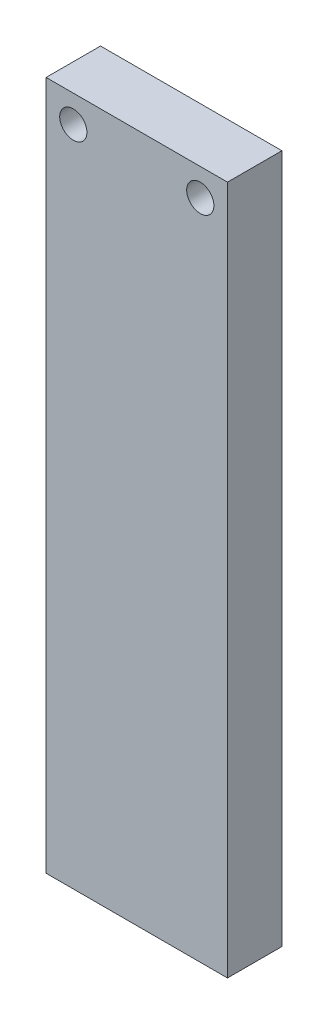
SolidWorks part; units mm, degrees
ref_plane "Plan de face" through (0, 0, 0) normal (0, 0, 1) x (1, 0, 0)
ref_plane "Plan de dessus" through (0, 0, 0) normal (0, 1, 0) x (1, 0, 0)
ref_plane "Plan de droite" through (0, 0, 0) normal (1, 0, 0) x (0, 0, -1)
sketch "Esquisse1" plane through (0, 0, 0) normal (0, 0, 1) x (1, 0, 0)
  line L1 (-10, 38) -> (10, 38)
  line L2 (-10, 38) -> (-10, -38)
  line L3 (-10, -38) -> (10, -38)
  line L4 (10, 38) -> (10, -38)
  dimension "D1" = 76
  dimension "D2" = 20
  dimension "D3" = 10
  dimension "D4" = 38
extrude "Boss.-Extru.1" add sketch "Esquisse1" along normal blind 6
sketch "Esquisse2" plane through (0, 0, 6) normal (0, 0, 1) x (1, 0, 0)
  line L0 (-21.2963, 35) -> (25.2376, 35) construction
  line L1 (10, 38) -> (-10, 38) construction
  line L2 (-10, 38) -> (-10, -38) construction
  line L3 (10, -38) -> (10, 38) construction
  circle A0 centre (-7, 35) radius 1.5
  circle A1 centre (7, 35) radius 1.5
  dimension "D1" = 3
  dimension "D2" = 3
  dimension "D4" = 3
  dimension "D5" = 3
  dimension "D3" = 3
extrude "Enlèv. mat.-Extru.1" cut sketch "Esquisse2" against normal blind 6
equation "\"D3@Esquisse1\"=\"D2@Esquisse1\"/2"
equation "\"D4@Esquisse1\"=\"D1@Esquisse1\"/2"
